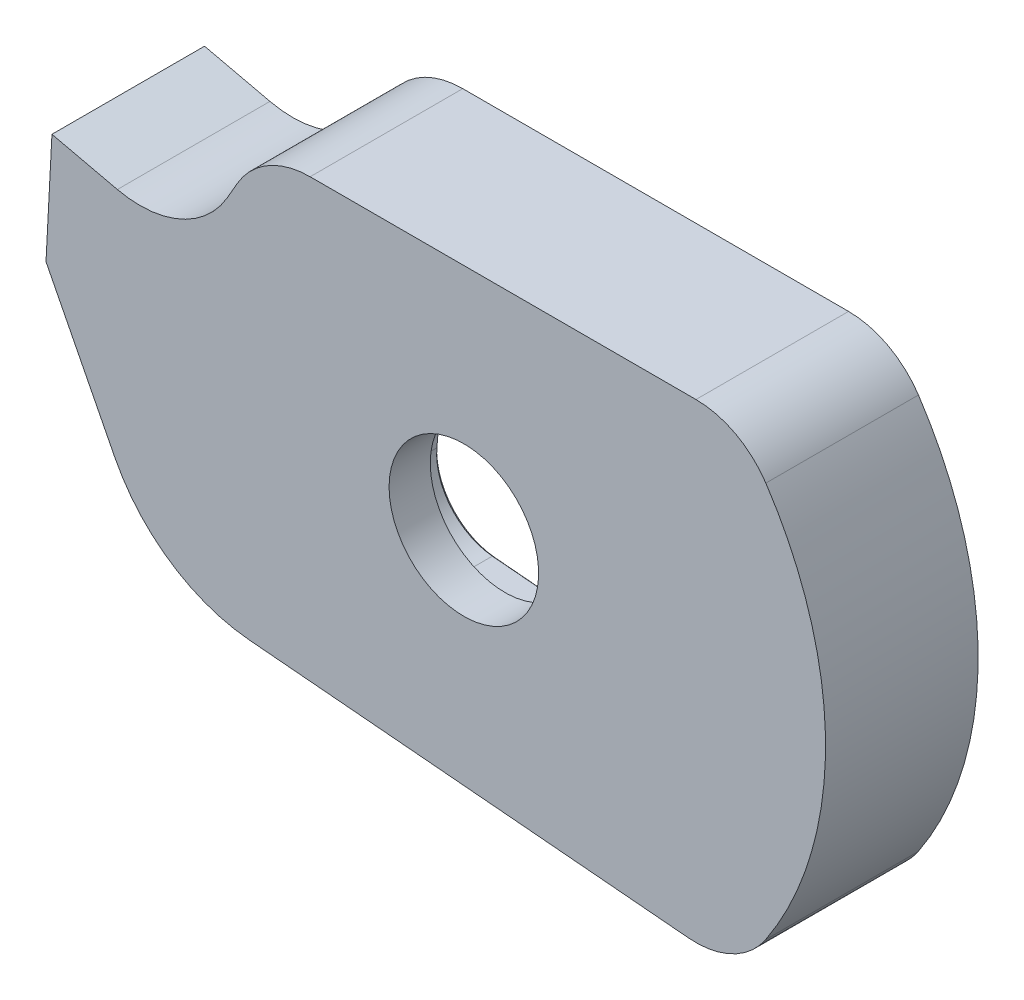
SolidWorks part; units mm, degrees
material "AISI 4340 Aço, normalizado"
ref_plane "Plano frontal" through (0, 0, 0) normal (0, 0, 1) x (1, 0, 0)
ref_plane "Plano superior" through (0, 0, 0) normal (0, 1, 0) x (1, 0, 0)
ref_plane "Plano direito" through (0, 0, 0) normal (1, 0, 0) x (0, 0, -1)
other "Center of Mass"
sketch "Sketch2" plane through (0, 0, 0) normal (0, 0, 1) x (1, 0, 0)
  line L0 (0, 0) -> (-50, 0) construction
  line L1 (-115.1603, 41.8011) -> (-136.5964, 46.75)
  line L2 (0, 0) -> (-142.97, 20.0931) construction
  line L5 (-51.9968, 77) -> (74.4153, 77)
  line L6 (0, 0) -> (0, 41.2714) construction
  line L8 (-75.8125, 63.25) -> (-79.158, 57.4553)
  line L14 (-71.7951, -64.424) -> (71.9488, -77)
  line L19 (-136.5964, 46.75) -> (-138.542, 9.625)
  line L20 (-137.1069, 44.5388) -> (-135.4014, 51.9262) construction
  line L22 (-138.542, 9.625) -> (-116.0069, -34.6028)
  circle A0 centre (0, 0) radius 144.375 construction
  arc A5 (74.4153, 77) -> (97.3123, 64.7308) centre (74.4153, 49.5) cw
  arc A6 (-51.9968, 77) -> (-75.8125, 63.25) centre (-51.9968, 49.5) ccw
  arc A17 (-116.0069, -34.6028) -> (-71.7951, -64.424) centre (-67.0015, -9.6333) ccw
  arc A18 (-115.1603, 41.8011) -> (-79.158, 57.4553) centre (-107.7369, 73.9553) ccw
  arc A20 (97.3123, 64.7308) -> (97.2212, -64.8676) centre (0, 0) cw
  arc A21 (71.9488, -77) -> (97.2212, -64.8676) centre (74.3456, -49.6046) ccw
  point P29 (-144.375, 0)
  point P31 (29.3939, 77)
  point P32 (-67.8739, 77)
  point P33 (97.3123, -64.7308)
  dimension "D1" = 288.75
  dimension "D4" = 27.5
  dimension "D5" = 33
  dimension "D13" = 27.5
  dimension "D11" = 55
  dimension "D10" = 77
  dimension "D2" = 5
  dimension "D3" = 10
  dimension "D7" = 30
  dimension "D8" = 77
  dimension "D12" = 30
  dimension "D9" = 46.75
  dimension "D14" = 37.125
  dimension "D15" = 22
  dimension "D6" = 27.5
  dimension "D16" = 5
  dimension "D17" = 77
extrude "EXTRUSÃO GEOMETRIA" add sketch "Sketch2" along normal blind 50 contours L5 A5 A20 A21 L14 A17 L22 L19 L1 A18 L8 A6
sketch "Esboço3"
  line L0 (119.5605, -25.8367) -> (117.6529, -4.0323)
  line L1 (125.3653, 6.5829) -> (138.542, 9.625)
  line L2 (138.542, 9.625) -> (116.0069, -34.6028) construction
  line L3 (138.542, 9.625) -> (116.0069, -34.6028)
  line L4 (71.7951, -64.424) -> (-71.9488, -77) construction
  line L5 (115.1603, 41.8011) -> (136.5964, 46.75) construction
  line L6 (31.1551, 77) -> (-22.8799, 20.2266)
  line L7 (51.9968, 77) -> (-74.4153, 77) construction
  line L8 (-28.0452, 17.3392) -> (-116.865, -1.5321)
  line L9 (31.1551, 77) -> (-74.4153, 77)
  arc A0 (71.7951, -64.424) -> (116.0069, -34.6028) centre (67.0015, -9.6333) ccw construction
  arc A1 (117.6529, -4.0323) -> (125.3653, 6.5829) centre (127.6148, -3.1608) cw
  arc A2 (119.5605, -25.8367) -> (116.0069, -34.6028) centre (67.0015, -9.6333) ccw
  arc A3 (-97.3123, 64.7308) -> (-97.2212, -64.8676) centre (0, 0) ccw construction
  arc A4 (-22.8799, 20.2266) -> (-28.0452, 17.3392) centre (-30.1235, 27.1209) cw
  arc A5 (-74.4153, 77) -> (-97.3123, 64.7308) centre (-74.4153, 49.5) ccw construction
  arc A6 (-97.3123, 64.7308) -> (-116.865, -1.5321) centre (0, 0) ccw
  arc A7 (-74.4153, 77) -> (-97.3123, 64.7308) centre (-74.4153, 49.5) ccw
  point P11 (-22.8799, 20.2266)
  point P24 (-36.8917, 15.4596)
  dimension "D1" = 10
  dimension "D3" = 10
  dimension "D2" = 22
sketch "Esboço3<3>" plane through (0, 0, 0) normal (0, 0, -1) x (-1, 0, 0) same geometry as "Esboço3"
other "Ponto de referência do centro da massa1"
ref_plane "Plano2" through (0, 1.9378, 0) normal (0, -1, 0) x (-1, 0, 0)
ref_plane "Plano3" through (-1.6368, 0, 0) normal (1, 0, 0) x (0, 0, -1)
sketch "Esboço2" plane through (0, 0, 0) normal (0, 0, -1) x (-1, 0, 0)
  line L0 (-8.25, 1.9378) -> (8.25, 1.9378) construction
  line L1 (-38.0236, 53.678) -> (31.7101, 59.7789)
  line L2 (-56.2044, 32.011) -> (-50.1035, -37.7226)
  line L3 (-28.4364, -55.9034) -> (41.2972, -49.8025)
  line L4 (53.3771, 41.5982) -> (59.478, -28.1355)
  line L5 (-57.9475, 51.9349) -> (61.2211, -48.0594) construction
  line L6 (-48.3603, -57.6465) -> (51.6339, 61.5221) construction
  line L7 (1.6368, 8.25) -> (1.6368, -8.25) construction
  line L8 (71.7951, -64.424) -> (-71.9488, -77) construction
  line L10 (2.503, 1.9378) -> (86.0271, 1.9378) construction
  circle A0 centre (1.6368, 1.9378) radius 24.5
  arc A2 (-38.0236, 53.678) -> (-56.2044, 32.011) centre (-36.2805, 33.7542) ccw
  arc A3 (31.7101, 59.7789) -> (53.3771, 41.5982) centre (33.4532, 39.8551) cw
  arc A4 (41.2972, -49.8025) -> (59.478, -28.1355) centre (39.5541, -29.8786) ccw
  arc A5 (-50.1035, -37.7226) -> (-28.4364, -55.9034) centre (-30.1796, -35.9795) ccw
  circle A6 centre (1.6368, 1.9378) radius 42.5
  dimension "D1" = 20
  dimension "D2" = 49
  dimension "D5" = 85
  dimension "D3" = 110
  dimension "D4" = 110
extrude "REBAIXO CAMISA" cut sketch "Esboço2" against normal blind 36.5 contours L1 A3 L4 A4 L3 A5 L2 A2
extrude "FURO EIXO" cut sketch "Esboço2<3>" against normal through all contours A0
sketch "Esboço2<3>" plane through (0, 0, 0) normal (0, 0, -1) x (-1, 0, 0) same geometry as "Esboço2"
chamfer "CHANFRO CAMISA" distance 1 angle 45 8 edges at (-6.4304, -52.8529, 0) (43.0353, -51.3004, 0) (-54.875, -42.7343, 0) (53.1539, -2.8558, 0) (-56.4275, 6.7314, 0) (51.6013, 46.6099, 0) (-46.3089, 55.1759, 0) (3.1568, 56.7285, 0)
equation "\"escala\" = 1                                            'projeto - escala geral"
equation "\"escala_disco-arma\"= 2.75                               'disco arma - escala geometria disco arma"
equation "\"rolamento_D-ext\"= 85                                   'rolamento arma - diametro externo"
equation "\"rolamento_d-int\"= 45                                   'rolamento arma - diametro interno"
equation "\"rolamento_b-esp\"= 23                                   'rolamento arma - espessura"
equation "\"arma_rebaixo-camisa_b\"= \"rolamento_b-esp\" + (\"arma-espessura\"-\"rolamento_b-esp\")/2        'disco arma - profundidade rebaixo camisa"
equation "\"arma_dente_altura-centro\" = 20 * \"escala_disco-arma\""
equation "\"arma-espessura\"= 50                                    'disco arma - espessura disco arma"
equation "\"D1@EXTRUSÃO GEOMETRIA\" = \"arma-espessura\""
equation "\"eixo_diam\"= \"rolamento_d-int\"                          'eixo arma - diametro"
equation "\"D2@Esboço2\" = \"eixo_diam\" + \"arma_eixo-furo_folga\""
equation "\"camisa_largura\"=110                                    'camisa arma - tamanho do lado"
equation "\"D3@Esboço2\"=\"camisa_largura\""
equation "\"camisa_raio\"=15                                        'camisa arma - raio canto interno"
equation "\"arma_rebaixo-camisa_raio\" = 5 + \"camisa_raio\"          'raio do rebaixo da camisa da arma "
equation "\"D1@Esboço2\"=\"arma_rebaixo-camisa_raio\""
equation "\"arma_alivio_raio\" = 12 * \"escala_disco-arma\""
equation "\"arma_diam_max\" = 105 * \"escala_disco-arma\""
equation "\"D1@Sketch2\" = \"arma_diam_max\""
equation "\"arma_arestas_raio\" = 10 * \"escala_disco-arma\""
equation "\"D4@Sketch2\" = \"arma_arestas_raio\""
equation "\"arma_altura_superior-centro\" = 28 * \"escala_disco-arma\""
equation "\"D10@Sketch2\" = \"arma_altura_superior-centro\""
equation "\"arma_dente_raio\" = 12 * \"escala_disco-arma\""
equation "\"D5@Sketch2\" = \"arma_dente_raio\""
equation "\"arma_altura_dente-centro\" = 17 * \"escala_disco-arma\""
equation "\"D9@Sketch2\"=\"arma_altura_dente-centro\""
equation "\"arma_dente_altura\" = 13.5 * \"escala_disco-arma\""
equation "\"arma_alivio-dente_raio\" = 20 * \"escala_disco-arma\""
equation "\"arma_traseira_offset\" = 10 * \"escala_disco-arma\""
equation "\"arma_centralizacao_offset\" = 8 * \"escala_disco-arma\""
equation "\"arma_eixo-furo_folga\" = 4                              'arma - folga entre furo arma e eixo"
equation "\"D1@REBAIXO CAMISA\" = \"arma_rebaixo-camisa_b\""
equation "\"arma_dente_comprimento\" = 8 * \"escala_disco-arma\""
equation "\"D15@Sketch2\"=\"arma_dente_comprimento\""
equation "\"D6@Sketch2\"=\"arma_traseira_offset\""
equation "\"D11@Sketch2\"=\"arma_alivio-dente_raio\""
equation "\"D4@Esboço2\"=\"camisa_largura\""
equation "\"D14@Sketch2\"=\"arma_dente_altura\""
equation "\"arma_altura_inferior-centro\" = 28 * \"escala_disco-arma\""
equation "\"D17@Sketch2\"=\"arma_altura_inferior-centro\""
equation "\"D13@Sketch2\"=\"arma_arestas_raio\""
equation "\"D5@Esboço2\"=\"rolamento_D-ext\""
